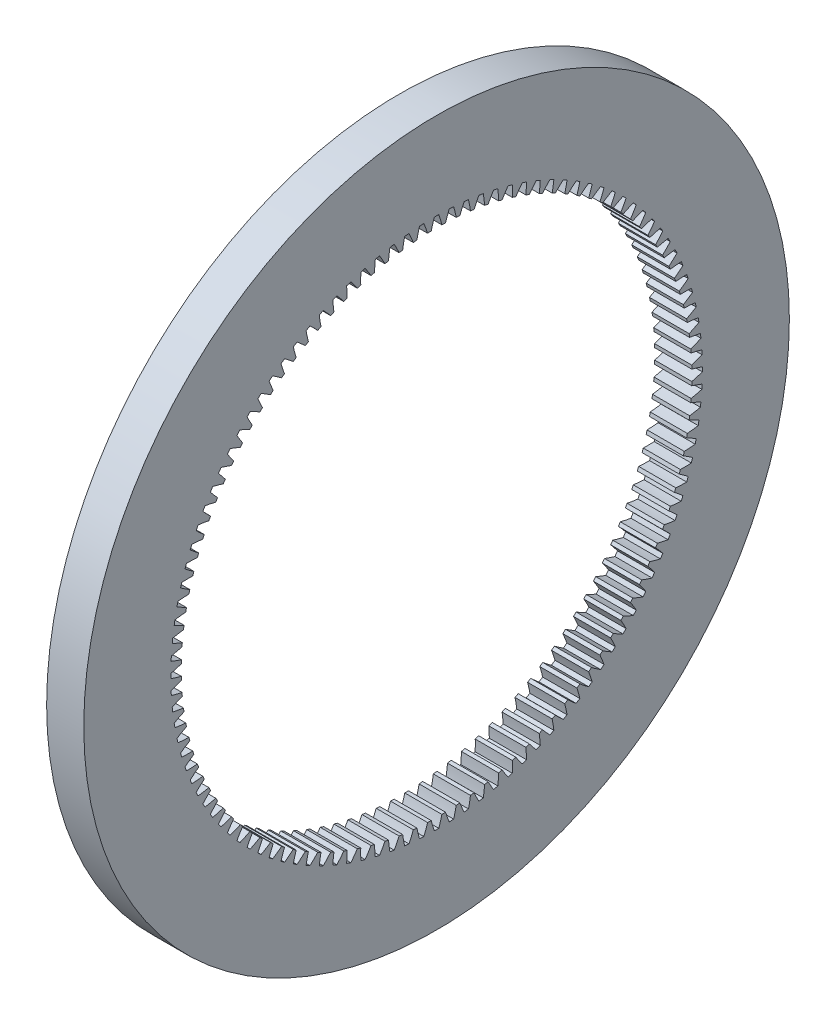
SolidWorks part; units mm, degrees
ref_plane "Plane1" through (0, 0, 0) normal (0, 0, 1) x (1, 0, 0)
ref_plane "Plane2" through (0, 0, 0) normal (0, 1, 0) x (1, 0, 0)
ref_plane "Plane3" through (0, 0, 0) normal (1, 0, 0) x (0, 0, -1)
sketch "HoldingSke" plane through (0, 0, 0) normal (0, 1, 0) x (1, 0, 0)
  line L0 (0, 0) -> (-0.2997, -0.7417)
  line L1 (-15, 0) -> (100, 0) construction
  line L2 (0, 0) -> (-2.1039, 2.3779)
  line L3 (0, 0) -> (-11.863, 4.5341)
  line L4 (0, 0) -> (-3.2351, 8.0072)
  line L5 (0, 0) -> (-23.7986, -8.8762)
  line L6 (0, 0) -> (-10.5278, -7.1032)
  line L7 (-2.1039, 2.3779) -> (3.3635, 27.1825)
  line L8 (-76.2, 3.6279) -> (-54.61, 3.6279)
  line L9 (-67.7845, 28.3722) -> (-49.3413, 33.142)
  line L10 (-76.2, 71.12) -> (104.1128, 71.12)
  line L11 (0, 0) -> (-10, 0)
  line L12 (-76.2, 101.6) -> (-76.155, 101.6)
  line L13 (24.9733, 27.94) -> (52.9518, 28.4284)
  line L14 (24.9733, 27.94) -> (24.9743, 27.94)
  line L15 (24.9733, 27.94) -> (100.4006, 29.5858)
  circle A0 centre (0, 0) radius 95
  circle A1 centre (0, 0) radius 12.7
  circle A2 centre (0, 0) radius 12.7
  dimension "Num_teeth" = 112
  dimension "Pitch_radius" = 180.3128
  dimension "Width" = 10
  dimension "Diameter" = 190
sketch "BasProSke" plane through (0, 0, 0) normal (0, 1, 0) x (1, 0, 0)
  line L0 (-10, 0) -> (60, 0) construction
  line L1 (0, 68.75) -> (0, 95)
  line L2 (0, 68.75) -> (10, 68.75)
  line L3 (10, 68.75) -> (10, 95)
  line L4 (10, 95) -> (0, 95)
  dimension "Thickness" = 10
  dimension "Diameter" = 190
revolve "Base-Revolve" add sketch "BasProSke" angle 360 about L0
sketch "TooCutSke" plane through (0, 0, 0) normal (1, 0, 0) x (0, 0, -1)
  line L3 (1.0942, 69.9914) -> (1.0942, 53.6633) construction
  line L4 (0, 0) -> (0, 59.563) construction
  line L5 (0, 0) -> (-1.9163, 68.3006) construction
  line L6 (-32.4807, 60.106) -> (36.1173, 62.0307) construction
  circle A0 centre (0, 0) radius 70 construction
  circle A1 centre (0, 0) radius 71.5635 construction
  circle A2 centre (0, 0) radius 60.9933 construction
  circle A3 centre (0, 0) radius 68.7246 construction
  arc A4 (1.4454, 68.7094) -> (0.5916, 71.5611) centre (-32.4807, 60.106) ccw
  arc A5 (1.4454, 68.7094) -> (-1.4454, 68.7094) centre (0, 0) ccw
  arc A6 (0.5916, 71.5611) -> (-0.5916, 71.5611) centre (0, 0) ccw
  arc A7 (-0.5916, 71.5611) -> (-1.4454, 68.7094) centre (32.4807, 60.106) ccw
extrude "ToothCut" cut sketch "TooCutSke" along normal through all
fillet "Breaks" [suppressed] radius 0.125
fillet "RootFillets" [suppressed] radius 0.3135
pattern_circular "TeethCuts" count 112 every 3.214 about axis through (-10, 0, 0) along (1, 0, 0) of "RootFillets", "Breaks", "ToothCut"
equation "' \"Module@HoldingSke\" = 6.35"
equation "' \"Num_teeth@HoldingSke\" = 24"
equation "' \"Ap@HoldingSke\" =  14.5"
equation "' \"Ap@HoldingSke\" = 14.5"
equation "' \"Width@HoldingSke\" = 12"
equation "' \"Diameter@HoldingSke\" = 8 * 25.4"
equation "' \"Show_teeth@HoldingSke\" = 100"
equation "' \"Backlash@HoldingSke\" = 0.009 * 25.4"
equation "' \"Addendum_fac@HoldingSke\" = 1.0"
equation "' \"Dedendum_fac@HoldingSke\" = 1.25"
equation "' \"Dedendum_add@HoldingSke\" = 0.00005 * 25.4"
equation "' \"Clearance_fac@HoldingSke\" = 0.25"
equation "\"Pitch@HoldingSke\" = 1 / \"Module@HoldingSke\" "
equation "\"Overcut_dia@TooCutSke\" = (\"Num_teeth@HoldingSke\" - 2 * \"Addendum_fac@HoldingSke\") / \"Pitch@HoldingSke\" - 0.002 * 25.4"
equation "\"Pitch_dia@TooCutSke\" = \"Num_teeth@HoldingSke\" / \"Pitch@HoldingSke\""
equation "\"Base_dia@TooCutSke\" = \"Num_teeth@HoldingSke\" / \"Pitch@HoldingSke\" * cos((\"Ap@HoldingSke\"  * 3.14159265 / 180)) * 0.90"
equation "\"Root_dia@TooCutSke\" = \"Num_teeth@HoldingSke\"  / \"Pitch@HoldingSke\" + 2 *  \"Dedendum_fac@HoldingSke\"/ \"Pitch@HoldingSke\" + \"Dedendum_add@HoldingSke\" * 2"
equation "\"Half_ang@TooCutSke\" = 180 / \"Num_teeth@HoldingSke\""
equation "\"Half_CT@TooCutSke\" = \"Num_teeth@HoldingSke\" / \"Pitch@HoldingSke\" * sin((3.14159265 / 2 / \"Num_teeth@HoldingSke\")) / 2 + 10 * \"Backlash@HoldingSke\" / 4"
equation "\"Flank_rad@TooCutSke\" = \"Num_teeth@HoldingSke\" / \"Pitch@HoldingSke\" / 4"
equation "\"Radius@RootFillets\"= \"Clearance_fac@HoldingSke\" / \"Pitch@HoldingSke\" + \"Dedendum_add@HoldingSke\""
equation "\"Break_rad@Breaks\" = 0.02 / \"Pitch@HoldingSke\" * 5"
equation "\"Num_teeth@TeethCuts\" = int( \"Show_teeth@HoldingSke\" ) + 1"
equation "\"Num_teeth@TeethCuts\" = ((sgn( \"Num_teeth@TeethCuts\" - \"Num_teeth@HoldingSke\" )-1)*( \"Num_teeth@TeethCuts\" - \"Num_teeth@HoldingSke\" ))/-2+ \"Num_teeth@HoldingSke\""
equation "\"Num_teeth@TeethCuts\" = ((sgn( \"Num_teeth@TeethCuts\" - 2.0)+1)*( \"Num_teeth@TeethCuts\" - 2.0))/2 +2.0"
equation "\"Angle@TeethCuts\" = 360.0 / \"Num_teeth@HoldingSke\""
equation "\"Diameter@BasProSke\" = \"Num_teeth@HoldingSke\"  / \"Pitch@HoldingSke\" + 2 *  \"Dedendum_fac@HoldingSke\"/ \"Pitch@HoldingSke\" + \"Dedendum_add@HoldingSke\" * 2 + 0.002 * 25.4"
equation "\"Diameter@BasProSke\" = ((sgn( \"Diameter@BasProSke\"  - \"Diameter@HoldingSke\" )+1)*( \"Diameter@BasProSke\"  - \"Diameter@HoldingSke\" ))/2 + \"Diameter@HoldingSke\""
equation "\"Inside_diameter@BasProSke\" =  (\"Num_teeth@HoldingSke\" - 2 * \"Addendum_fac@HoldingSke\") / \"Pitch@HoldingSke\" "
equation "\"Thickness@BasProSke\"  = \"Width@HoldingSke\""
